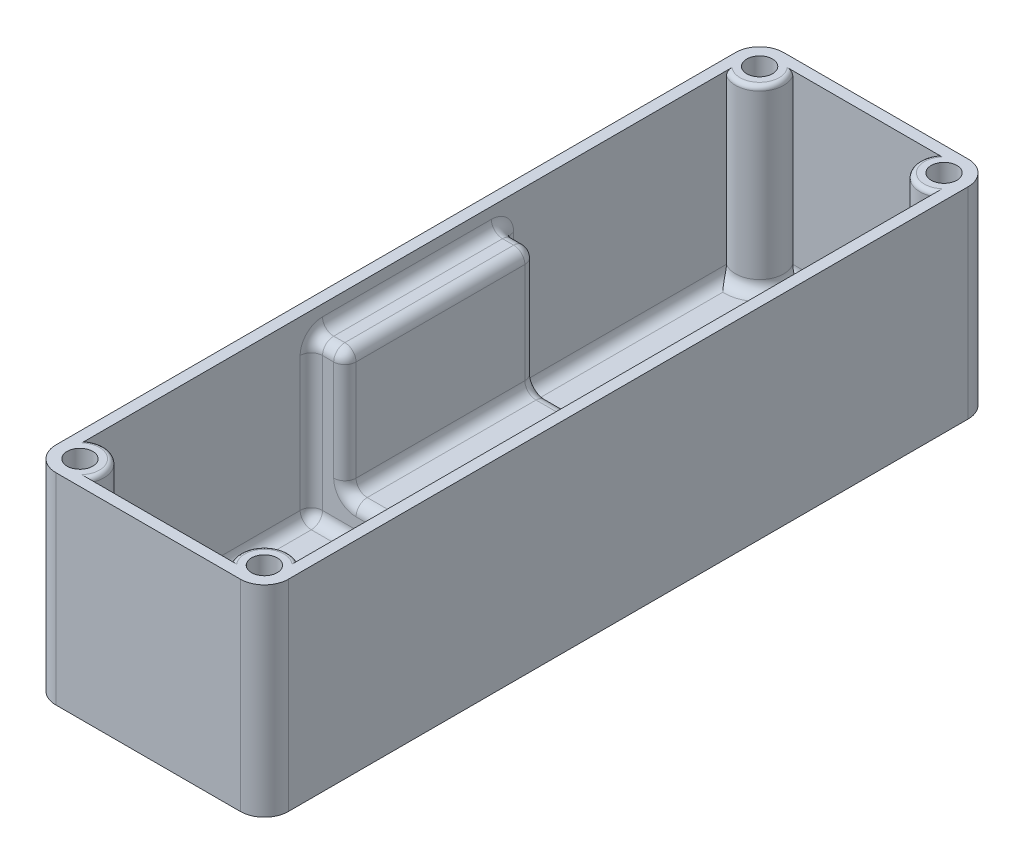
SolidWorks part; units mm, degrees
ref_plane "前视基准面" through (0, 0, 0) normal (0, 0, 1) x (1, 0, 0)
ref_plane "上视基准面" through (0, 0, 0) normal (0, 1, 0) x (1, 0, 0)
ref_plane "右视基准面" through (0, 0, 0) normal (1, 0, 0) x (0, 0, -1)
sketch "草图1" plane through (0, 0, 0) normal (0, 1, 0) x (1, 0, 0)
  line L0 (4.6439, -13.55) -> (-3.906, -13.55) construction
  line L1 (-8.25, 30.4) -> (8.25, 30.4) construction
  line L2 (-8.25, 30.4) -> (-8.25, -30.4) construction
  line L3 (-8.25, -30.4) -> (8.25, -30.4) construction
  line L4 (8.25, 30.4) -> (8.25, -30.4) construction
  line L5 (-8.25, 30.4) -> (8.25, -30.4) construction
  line L6 (-8.25, -30.4) -> (8.25, 30.4) construction
  line L11 (-6.4334, 31.55) -> (6.4334, 31.55)
  line L12 (-9.4, 28.5834) -> (-9.4, -28.5834)
  line L13 (-8.25, 32.55) -> (8.25, 32.55)
  line L14 (-10.4, 30.4) -> (-10.4, -30.4)
  line L15 (-8.25, -32.55) -> (8.25, -32.55)
  line L16 (10.4, 30.4) -> (10.4, -30.4)
  line L17 (-6.4334, -31.55) -> (6.4334, -31.55)
  line L18 (9.4, 28.5834) -> (9.4, -28.5834)
  line L19 (-9.2345, 30.9944) -> (9.2345, -30.9944) construction
  line L20 (-9.2345, -30.9944) -> (9.2345, 30.9944) construction
  line L22 (-4.55, -8.55) -> (-0.05, -8.55)
  line L23 (-4.55, -8.55) -> (-4.55, -18.55)
  line L24 (-4.55, -18.55) -> (-0.05, -18.55)
  line L25 (-0.05, -8.55) -> (-0.05, -18.55)
  line L26 (-4.55, -8.55) -> (-0.05, -18.55) construction
  line L27 (-4.55, -18.55) -> (-0.05, -8.55) construction
  circle A0 centre (-8.25, 30.4) radius 1.15
  circle A1 centre (8.25, 30.4) radius 1.15
  circle A2 centre (8.25, -30.4) radius 1.15
  circle A3 centre (-8.25, -30.4) radius 1.15
  circle A4 centre (-8.25, 30.4) radius 2.15
  circle A5 centre (8.25, 30.4) radius 2.15
  circle A6 centre (8.25, -30.4) radius 2.15
  circle A7 centre (-8.25, -30.4) radius 2.15
  circle A8 centre (2.9, -13.55) radius 1.1
  circle A9 centre (2.9, -13.55) radius 2.1
  point P0 (0, 0)
  point P8 (0, 0)
  point P25 (0, 0)
  point P26 (0, 0)
  point P48 (-2.3, -13.55)
  dimension "D3" = 2.3
  dimension "D6" = 1
  dimension "D7" = 2
  dimension "D11" = 2.2
  dimension "D14" = 1
  dimension "D1" = 16.5
  dimension "D2" = 60.8
  dimension "D8" = 1
  dimension "D9" = 1
  dimension "D12" = 18
  dimension "D13" = 6.5
  dimension "D15" = 5.2
  dimension "D16" = 4.5
  dimension "D17" = 10
  dimension "D4" = 2
  dimension "D5" = 2
  dimension "D10" = 2
extrude "凸台-拉伸1" add sketch "草图1" along normal blind 2 contours A7 L17 A6 L18 A5 L11 A4 L12 A9 L22 L25 L24 L23 | A7 L12 A4 L14 | A7 A3 | A7 L15 A6 L17 | A6 A2 | A6 L16 A5 L18 | A3 | A2 | A9 A8 | A8 | A4 A0 | A0 | A5 A1 | A1 | A5 L13 A4 L11 region at (0, 0, -32.0667) region at (0.0582, 0, -0.7324) region at (-6.2434, 0, -30.9817) region at (7.2425, 0, -32.2302) region at (9.904, 0, 0) region at (-9.904, 0, 0) region at (10.0802, 0, 29.3925) region at (-7.2425, 0, 28.5698) region at (0, 0, 32.0667) region at (-8.25, 0, -30.4) region at (8.25, 0, -30.4) region at (8.25, 0, 30.4) region at (-8.25, 0, 30.4) region at (2.9, 0, 13.55) region at (0.8594, 0, 13.55)
extrude "凸台-拉伸2" add sketch "草图1<7>" along normal blind 8 contours A9 A8 region at (0.8594, 0, 13.55)
sketch "草图1<7>" plane through (0, 0, 0) normal (0, 1, 0) x (1, 0, 0) same geometry as "草图1"
extrude "凸台-拉伸3" add sketch "草图1<9>" along normal blind 18 contours A7 A3 | A7 L12 A4 L14 | A7 L15 A6 L17 | A6 A2 | A6 L16 A5 L18 | A4 A0 | A5 L13 A4 L11 | A5 A1 region at (0, 0, -32.0667) region at (-6.2434, 0, -30.9817) region at (7.2425, 0, -32.2302) region at (9.904, 0, 0) region at (-9.904, 0, 0) region at (10.0802, 0, 29.3925) region at (-7.2425, 0, 28.5698) region at (0, 0, 32.0667)
sketch "草图1<9>" plane through (0, 0, 0) normal (0, 1, 0) x (1, 0, 0) same geometry as "草图1"
fillet "圆角4" radius 1 4 edges at (-0.05, 1, 18.55) (-4.55, 1, 18.55) (-4.55, 1, 8.55) (-0.05, 1, 8.55)
fillet "圆角6" radius 0.4 4 edges at (-6.7297, 18, 28.8797) (6.7297, 18, 28.8797) (6.7297, 18, -28.8797) (-6.7297, 18, -28.8797)
sketch "草图4" plane through (-10.4, 0, 0) normal (-1, 0, 0) x (0, 0, 1)
  line L0 (-30.4, 9) -> (30.4, 9) construction
  line L1 (-7.1, 13.6) -> (7.1, 13.6)
  line L2 (-7.1, 13.6) -> (-7.1, 4.4)
  line L3 (-7.1, 4.4) -> (7.1, 4.4)
  line L4 (7.1, 13.6) -> (7.1, 4.4)
  line L5 (-7.1, 13.6) -> (7.1, 4.4) construction
  line L6 (-7.1, 4.4) -> (7.1, 13.6) construction
  line L7 (-30.4, 18) -> (-30.4, 0) construction
  line L8 (30.4, 18) -> (30.4, 0) construction
  line L9 (-30.4, 0) -> (30.4, 0) construction
  line L10 (-8.55, 16) -> (8.55, 16)
  line L11 (-8.55, 16) -> (-8.55, 2)
  line L12 (-8.55, 2) -> (8.55, 2)
  line L13 (8.55, 16) -> (8.55, 2)
  line L14 (-8.55, 16) -> (8.55, 2) construction
  line L15 (-8.55, 2) -> (8.55, 16) construction
  point P0 (0, 9)
  point P12 (0, 9)
  dimension "D1" = 9.2
  dimension "D2" = 14.2
  dimension "D3" = 2
  dimension "D4" = 8.55
extrude "凸台-拉伸4" add sketch "草图4" against normal blind 4 contours L4 L1 L2 L3 | L13 L10 L11 L12 L1 L4 L3 L2 region at (-10.4, 9, 0) region at (-10.4, 15.779, 0)
extrude "切除-拉伸2" cut sketch "草图4<3>" against normal blind 3 contours L4 L1 L2 L3 region at (-10.4, 9, 0)
sketch "草图4<3>" plane through (-10.4, 0, 0) normal (-1, 0, 0) x (0, 0, 1) same geometry as "草图4"
fillet "圆角10" radius 1 1 edges at (2.9, 2, 15.65)
sketch "草图5" plane through (0, 0, 0) normal (0, -1, 0) x (1, 0, 0)
  line L0 (-3.55, 8.55) -> (-1.05, 8.55) construction
  line L1 (-4.6, 7.1) -> (4.6, 7.1)
  line L2 (-4.6, 7.1) -> (-4.6, -7.1)
  line L3 (-4.6, -7.1) -> (4.6, -7.1)
  line L4 (4.6, 7.1) -> (4.6, -7.1)
  line L5 (-4.6, 7.1) -> (4.6, -7.1) construction
  line L6 (-4.6, -7.1) -> (4.6, 7.1) construction
  line L7 (-6.6, 8.55) -> (6.6, 8.55)
  line L8 (-6.6, 8.55) -> (-6.6, -8.55)
  line L9 (-6.6, -8.55) -> (6.6, -8.55)
  line L10 (6.6, 8.55) -> (6.6, -8.55)
  line L11 (-6.6, 8.55) -> (6.6, -8.55) construction
  line L12 (-6.6, -8.55) -> (6.6, 8.55) construction
  point P0 (0, 0)
  point P7 (0, 0)
  line M9 (-1.05, 8.55) -> (-3.55, 8.55)
  dimension "D1" = 9.2
  dimension "D2" = 14.2
  dimension "D3" = 2
  dimension "D4" = 0
extrude "凸台-拉伸5" add sketch "草图5" against normal blind 5 contours L4 L1 L2 L3 | L10 L7 L8 L9 L1 L4 L3 L2 M9 region at (0, 0, 0) region at (-5.075, 0, 8.334)
extrude "切除-拉伸3" cut sketch "草图5<3>" against normal blind 3 contours L4 L1 L2 L3 region at (0, 0, 0)
sketch "草图5<3>" plane through (0, 0, 0) normal (0, -1, 0) x (1, 0, 0) same geometry as "草图5"
fillet "圆角11" radius 1 17 edges at (6.6, 2, 0) (-9.4, 9, 8.55) (6.6, 3.5, 8.55) (2.775, 2, 8.55) (6.6, 5, 0) (0.1, 5, 8.55) (-6.4, 10.5, 8.55) (-6.4, 5, 0) (-6.4, 16, 0) (-7.9, 16, 8.55) (-9.4, 16, 0) (6.6, 3.5, -8.55) (0.1, 5, -8.55) (-6.4, 10.5, -8.55) (-7.9, 16, -8.55) (-9.4, 9, -8.55) (-1.4, 2, -8.55)
fillet "圆角12" radius 1 12 edges at (-9.1071, 2.2929, -8.8429) (-6.7297, 2, 28.8797) (0, 2, 31.55) (6.7297, 2, 28.8797) (-9.4, 2, 19.0667) (-9.4, 2, -19.0667) (-6.7297, 2, -28.8797) (0, 2, -31.55) (6.7297, 2, -28.8797) (9.4, 2, 0) (-5.975, 2, 8.55) (-9.1071, 2, 8.8429)
